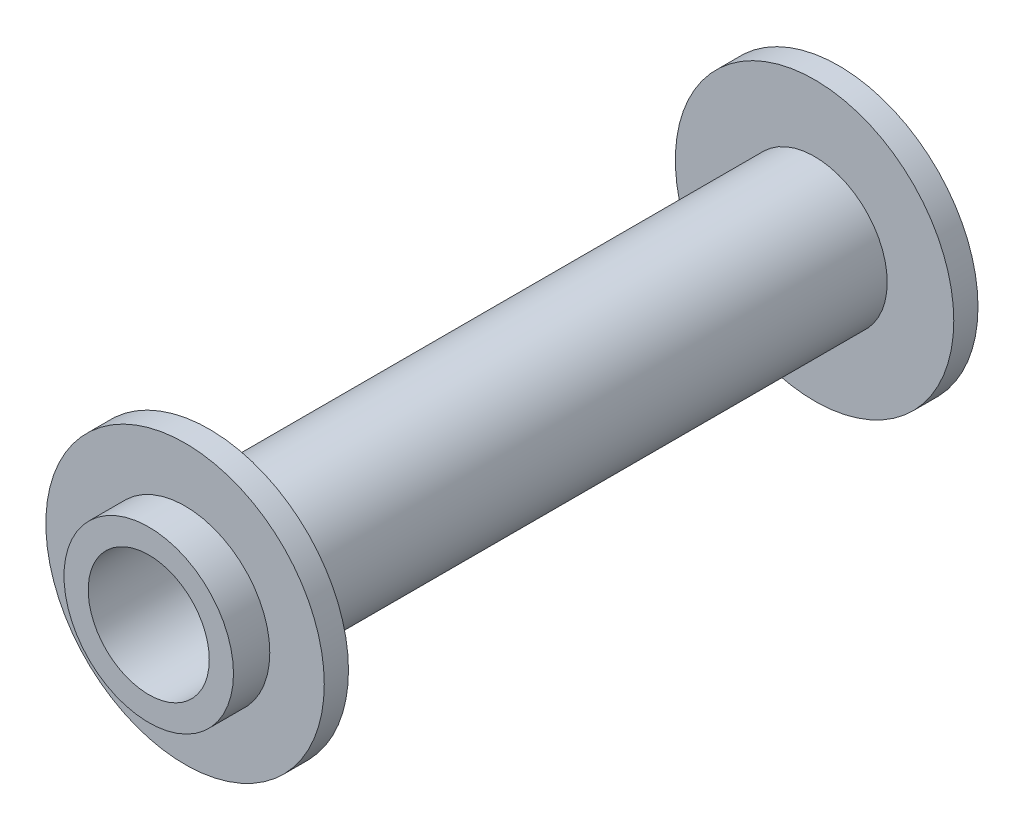
SolidWorks part; units mm, degrees
material "POM Acetal Copolymer"
ref_plane "Front Plane" through (0, 0, 0) normal (0, 0, 1) x (1, 0, 0)
ref_plane "Top Plane" through (0, 0, 0) normal (0, 1, 0) x (1, 0, 0)
ref_plane "Right Plane" through (0, 0, 0) normal (1, 0, 0) x (0, 0, -1)
sketch "Sketch2" plane through (0, 0, 0) normal (1, 0, 0) x (0, 0, -1)
  line L0 (0, 0) -> (56.7425, 0) construction
  line L1 (0, 5) -> (0, 7)
  line L2 (5, 6) -> (5, 11.5)
  line L3 (5, 11.5) -> (3, 11.5)
  line L4 (3, 11.5) -> (3, 7)
  line L5 (3, 7) -> (0, 7)
  line L6 (5, 6) -> (55, 6)
  line L7 (55, 6) -> (55, 11.5)
  line L8 (55, 11.5) -> (57, 11.5)
  line L9 (57, 11.5) -> (57, 7)
  line L10 (57, 7) -> (60, 7)
  line L11 (60, 7) -> (60, 5)
  line L12 (60, 5) -> (0, 5)
  dimension "D1" = 11.5
  dimension "D2" = 2
  dimension "D3" = 2
  dimension "D4" = 1
  dimension "D5" = 50
  dimension "D6" = 5
  dimension "D8" = 3
revolve "Revolve1" add sketch "Sketch2" angle 360 about L0
